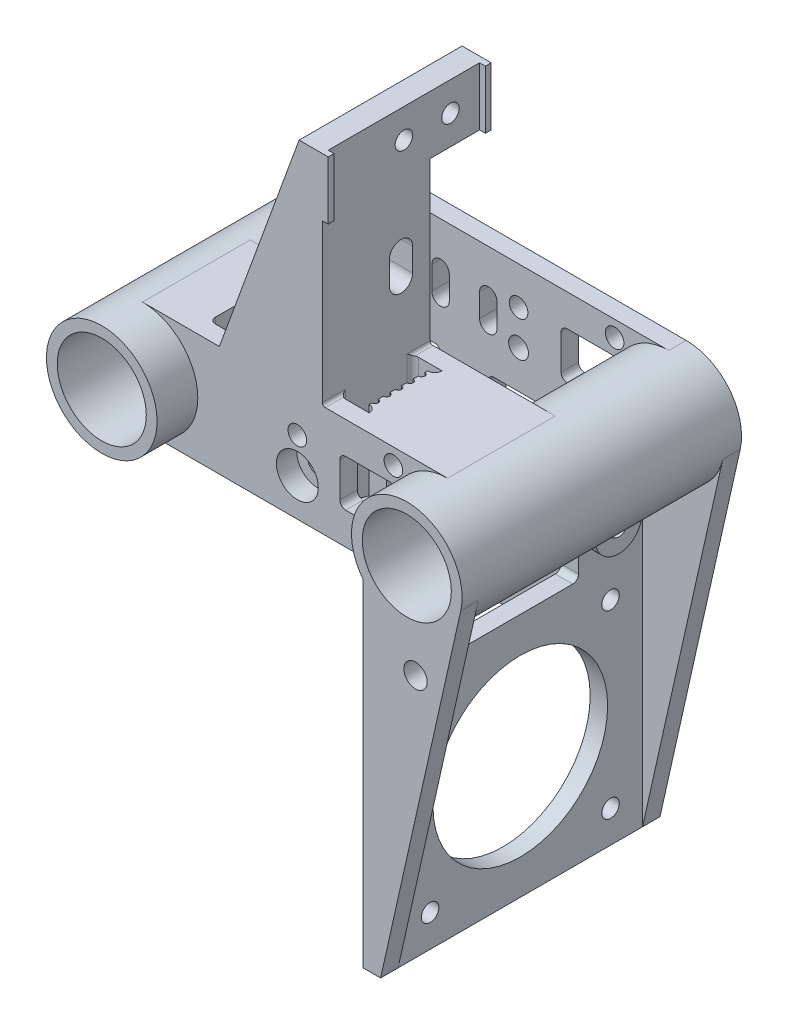
SolidWorks part; units mm, degrees
material "PET"
ref_plane "Front Plane" through (0, 0, 0) normal (0, 0, 1) x (1, 0, 0)
ref_plane "Top Plane" through (0, 0, 0) normal (0, 1, 0) x (1, 0, 0)
ref_plane "Right Plane" through (0, 0, 0) normal (1, 0, 0) x (0, 0, -1)
sketch "Sketch1" plane through (0, 0, 0) normal (0, 0, 1) x (1, 0, 0)
  circle A14 centre (0, 0) radius 7.65
  circle A15 centre (52.4, 0) radius 7.65
  circle A16 centre (0, 0) radius 9.5
  circle A17 centre (52.4, 0) radius 9.5
extrude "Boss-Extrude1" add sketch "Sketch1" along normal blind 48
sketch "Sketch29" plane through (0, 0, 0) normal (0, 0, -1) x (-1, 0, 0)
  line L5 (-42.3861, 4) -> (-34.9, 4)
  line L6 (-52.4, 9.5) -> (0, 9.5)
  line L7 (-33.9, 3) -> (-33.9, -3)
  line L9 (-34.9, -4) -> (-42.3861, -4)
  line L10 (-61.6706, -2.075) -> (-47.9, -63.6)
  line L12 (-47.9, -63.6) -> (-44.9, -63.6)
  line L13 (0.2114, -42.55) -> (9.2706, -2.075)
  line L21 (-44.9, -63.6) -> (-44.9, -42.55)
  line L24 (-44.9, -42.55) -> (0.2114, -42.55)
  line L25 (-7.5, -10.5) -> (-7.5, -24.5)
  line L26 (-12.2, -25.5) -> (-8.5, -25.5)
  line L27 (-13.2, -10.5) -> (-13.2, -24.5)
  line L28 (-12.2, -9.5) -> (-8.5, -9.5)
  line L30 (-11.7, 2) -> (-11.7, -2)
  line L32 (-14.7, 2) -> (-14.7, -2)
  line L35 (-21.4, -10.5) -> (-21.4, -24.5)
  line L36 (-19.9, 2) -> (-19.9, -2)
  line L37 (-22.9, 2) -> (-22.9, -2)
  line L38 (-44.9, -10.5) -> (-44.9, -24.5)
  line L39 (-43.9, -9.5) -> (-22.4, -9.5)
  line L40 (-43.9, -25.5) -> (-22.4, -25.5)
  arc A2 (-43.3861, 3) -> (-52.4, 9.5) centre (-52.4, 0) ccw
  arc A4 (-11.7, 2) -> (-14.7, 2) centre (-13.2, 2) ccw
  arc A6 (-42.3861, -4) -> (-43.3861, -3) centre (-42.3861, -3) cw
  arc A7 (-42.3861, 4) -> (-43.3861, 3) centre (-42.3861, 3) ccw
  arc A8 (-43.3861, -3) -> (-61.6706, -2.075) centre (-52.4, 0) cw
  arc A9 (-34.9, 4) -> (-33.9, 3) centre (-34.9, 3) cw
  arc A11 (-33.9, -3) -> (-34.9, -4) centre (-34.9, -3) cw
  arc A15 (9.2706, -2.075) -> (0, 9.5) centre (0, 0) cw
  arc A20 (-8.5, -9.5) -> (-7.5, -10.5) centre (-8.5, -10.5) cw
  arc A21 (-12.2, -9.5) -> (-13.2, -10.5) centre (-12.2, -10.5) ccw
  arc A22 (-13.2, -24.5) -> (-12.2, -25.5) centre (-12.2, -24.5) ccw
  arc A23 (-8.5, -25.5) -> (-7.5, -24.5) centre (-8.5, -24.5) ccw
  circle A24 centre (-10.3, -36.55) radius 1.5
  circle A25 centre (-24.3, -36.55) radius 1.5
  arc A27 (-14.7, -2) -> (-11.7, -2) centre (-13.2, -2) ccw
  arc A30 (-19.9, 2) -> (-22.9, 2) centre (-21.4, 2) ccw
  arc A31 (-22.9, -2) -> (-19.9, -2) centre (-21.4, -2) ccw
  arc A32 (-22.4, -9.5) -> (-21.4, -10.5) centre (-22.4, -10.5) cw
  arc A33 (-22.4, -25.5) -> (-21.4, -24.5) centre (-22.4, -24.5) ccw
  arc A34 (-43.9, -9.5) -> (-44.9, -10.5) centre (-43.9, -10.5) ccw
  arc A35 (-44.9, -24.5) -> (-43.9, -25.5) centre (-43.9, -24.5) ccw
  circle A36 centre (-43.0932, 6.75) radius 1.6
  circle A37 centre (-43.0932, -6.75) radius 1.6
  circle A38 centre (-26.5962, 3) radius 1.6
  circle A39 centre (-26.5962, -3) radius 1.7
extrude "Boss-Extrude18" add sketch "Sketch29" against normal blind 3
sketch "Sketch36" plane through (0, 0, 3) normal (0, 0, 1) x (1, 0, 0)
  line L0 (31.4, 9.5) -> (52.4, 9.5)
  line L1 (0, 9.5) -> (26.4, 9.5)
  line L2 (0, -9.5) -> (52.4, -9.5)
  line L3 (38.9, 3) -> (38.9, -3)
  line L4 (39.9, -4) -> (42.3861, -4)
  line L5 (39.9, 4) -> (42.3861, 4)
  line L6 (30.9, 10) -> (30.9, 37.05)
  line L7 (30.9, 37.05) -> (26.9, 37.05)
  line L8 (26.9, 37.05) -> (26.9, 10)
  arc A0 (0, 9.5) -> (0, -9.5) centre (0, 0) cw
  arc A1 (30.9, 10) -> (31.4, 9.5) centre (31.4, 10) ccw
  arc A2 (52.4, 9.5) -> (43.3861, 3) centre (52.4, 0) ccw
  arc A3 (26.9, 10) -> (26.4, 9.5) centre (26.4, 10) cw
  arc A4 (39.9, 4) -> (38.9, 3) centre (39.9, 3) ccw
  arc A7 (42.3861, 4) -> (43.3861, 3) centre (42.3861, 3) cw
  arc A8 (42.3861, -4) -> (43.3861, -3) centre (42.3861, -3) ccw
  arc A9 (38.9, -3) -> (39.9, -4) centre (39.9, -3) ccw
  arc A11 (43.3861, -3) -> (52.4, -9.5) centre (52.4, 0) ccw
  circle A13 centre (26.5962, -3) radius 1.7
  circle A14 centre (26.5962, 3) radius 1.6
  circle A15 centre (43.0932, -6.75) radius 1.6
  circle A16 centre (43.0932, 6.75) radius 1.6
  point P12 (30.9, 9.5)
extrude "Boss-Extrude26" add sketch "Sketch36" along normal blind 18.5 from offset 19.5
sketch "Sketch24" plane through (0, -9.5, 0) normal (0, -1, 0) x (1, 0, 0)
  line L14 (8.5, 37) -> (8.5, 26.5)
  line L15 (9.5, 25.5) -> (12.2, 25.5)
  line L27 (31.9, 38) -> (35.945, 38)
  line L28 (34.695, 33.195) -> (34.695, 32.305)
  line L29 (34.695, 31.195) -> (34.695, 30.305)
  line L30 (30.9, 26.5) -> (30.9, 37)
  line L31 (34.695, 28.305) -> (34.695, 29.195)
  line L32 (34.695, 34.305) -> (34.695, 35.195)
  line L33 (31.9, 25.5) -> (35.945, 25.5)
  line L34 (34.695, 36.75) -> (34.695, 36.305)
  line L35 (34.695, 27.195) -> (34.695, 26.75)
  line L36 (21.4, 37) -> (21.4, 35.4282)
  line L40 (9.5, 38) -> (20.4, 38)
  line L43 (12.2, 25.5) -> (14.6918, 25.5)
  arc A1 (8.5, 37) -> (9.5, 38) centre (9.5, 37) cw
  arc A3 (8.5, 26.5) -> (9.5, 25.5) centre (9.5, 26.5) ccw
  arc A15 (34.695, 36.305) -> (34.695, 35.195) centre (34.695, 35.75) cw
  arc A16 (34.695, 29.195) -> (34.695, 30.305) centre (34.695, 29.75) ccw
  arc A17 (34.695, 31.195) -> (34.695, 32.305) centre (34.695, 31.75) ccw
  arc A18 (34.695, 33.195) -> (34.695, 34.305) centre (34.695, 33.75) ccw
  arc A19 (34.695, 27.195) -> (34.695, 28.305) centre (34.695, 27.75) ccw
  arc A20 (30.9, 26.5) -> (31.9, 25.5) centre (31.9, 26.5) ccw
  arc A21 (30.9, 37) -> (31.9, 38) centre (31.9, 37) cw
  arc A22 (35.945, 38) -> (34.695, 36.75) centre (34.695, 38) cw
  arc A23 (34.695, 26.75) -> (35.945, 25.5) centre (34.695, 25.5) cw
  arc A30 (21.4, 37) -> (20.4, 38) centre (20.4, 37) ccw
  arc A31 (21.4, 35.4282) -> (20.5429, 34.4385) centre (20.4, 35.4282) cw
  arc A32 (20.5429, 34.4385) -> (15.6501, 26.7857) centre (21.4, 28.5) ccw
  arc A33 (14.6918, 25.5) -> (15.6501, 26.7857) centre (14.6918, 26.5) ccw
extrude "Cut-Extrude15" cut sketch "Sketch24" against normal up to surface (46.55 mm away) up to face at (28.9, 37.05, 31.75)
sketch "Sketch14" plane through (0, -9.5, 0) normal (0, -1, 0) x (1, 0, 0)
  circle A0 centre (21.4, 28.5) radius 4.125
extrude "Boss-Extrude27" add sketch "Sketch14" along normal blind 4
sketch "Sketch37" plane through (13.2, 0, 0) normal (-1, 0, 0) x (0, 0, 1)
  line L0 (3, -25.5) -> (3, -10)
  line L3 (22.5, 9.5) -> (3, -10)
  line L4 (22.5, 9.5) -> (22.5, -9.5)
  line L7 (3, -25.5) -> (20.0185, -8.4815)
  arc A1 (22.5, -9.5) -> (20.0185, -8.4815) centre (21.0502, -9.5) ccw
extrude "Boss-Extrude28" add sketch "Sketch37" against normal up to surface (8.2 mm away) up to face at (21.4, -17.5, 1.5)
sketch "Sketch34" plane through (0, 9.5, 0) normal (0, 1, 0) x (1, 0, 0)
  circle A2 centre (21.4, -28.5) radius 4.175
extrude "Cut-Extrude17" cut sketch "Sketch34" against normal blind 4.5
sketch "Sketch38" plane through (0, 5, 0) normal (0, 1, 0) x (1, 0, 0)
  circle A1 centre (21.4, -28.5) radius 2.15
extrude "Cut-Extrude18" cut sketch "Sketch38" against normal up to surface (18.5 mm away) up to face at (21.4, -13.5, 24.375)
sketch "Sketch7" plane through (0, 0, 48) normal (0, 0, 1) x (1, 0, 0)
  line L8 (61.6706, -2.075) -> (47.9, -63.6)
  line L10 (44.9, -5.831) -> (44.9, -63.6)
  line L11 (47.9, -63.6) -> (44.9, -63.6)
  circle A2 centre (53.9, -15.6) radius 2
  arc A8 (61.6706, -2.075) -> (44.9, -5.831) centre (52.4, 0) cw
extrude "Boss-Extrude30" add sketch "Sketch7" against normal blind 3
sketch "Sketch39" plane through (0, 0, 3) normal (0, 0, 1) x (1, 0, 0)
  line L0 (44.9, -63.6) -> (44.9, -21.5)
  line L2 (47.9, -21.5) -> (47.9, -63.6)
  line L3 (47.9, -63.6) -> (44.9, -63.6)
  line L5 (47.9, -21.5) -> (44.9, -21.5)
extrude "Boss-Extrude31" add sketch "Sketch39" along normal up to surface (42 mm away) up to face at (51.9, -15.6, 45)
sketch "Sketch61" plane through (0, 0, 3) normal (0, 0, 1) x (1, 0, 0)
  line L0 (52.4, -9.5) -> (47.9, -9.5)
  line L1 (44.9, -5.831) -> (44.9, -21.5)
  line L2 (44.9, -21.5) -> (47.9, -21.5)
  line L3 (47.9, -21.5) -> (47.9, -9.5)
  arc A0 (44.9, -5.831) -> (52.4, -9.5) centre (52.4, 0) ccw
extrude "Boss-Extrude39" add sketch "Sketch61" along normal blind 11
sketch "Sketch40" plane through (0, 0, 45) normal (0, 0, -1) x (-1, 0, 0)
  line L12 (-51.45, -12) -> (-50.5, -12)
  line L13 (-51.45, -12) -> (-51.45, -19)
  line L14 (-51.45, -19) -> (-50.5, -19)
  line L15 (-50.5, -12) -> (-50.5, -19)
  line L16 (-49.4, -12) -> (-47.9, -12)
  line L17 (-49.4, -12) -> (-49.4, -19)
  line L18 (-49.4, -19) -> (-47.9, -19)
  line L19 (-47.9, -12) -> (-47.9, -19)
extrude "Boss-Extrude32" add sketch "Sketch40" along normal blind 0.3
sketch "Sketch47" plane through (47.9, 0, 0) normal (1, 0, 0) x (0, 0, -1)
  circle A0 centre (-8.5, -15.55) radius 1.5
  circle A1 centre (-8.5, -15.55) radius 4
extrude "Boss-Extrude40" add sketch "Sketch47" along normal blind 1.4
sketch "Sketch20" plane through (47.9, 0, 0) normal (1, 0, 0) x (0, 0, -1)
  circle A0 centre (-8.5, -58.1) radius 1.5
  circle A1 centre (-39.5, -58.1) radius 1.5
  circle A2 centre (-8.5, -27.1) radius 1.5
  circle A3 centre (-24, -42.6) radius 15
  circle A5 centre (-8.5, -15.55) radius 1.5
extrude "Cut-Extrude19" cut sketch "Sketch20" against normal up to surface (3 mm away) up to face at (44.9, -24.9017, 16.1429)
sketch "Sketch43" plane through (0, 0, 41) normal (0, 0, 1) x (1, 0, 0)
  circle A1 centre (26.5962, -3) radius 3.6
extrude "Cut-Extrude22" cut sketch "Sketch43" against normal blind 3.5
sketch "Sketch45" plane through (0, 0, 41) normal (0, 0, 1) x (1, 0, 0)
  line L0 (33.9, 3) -> (33.9, -3)
  line L1 (34.9, 4) -> (42.3861, 4)
  line L2 (34.9, -4) -> (42.3861, -4)
  arc A0 (42.3861, 4) -> (43.3861, 3) centre (42.3861, 3) cw
  arc A1 (43.3861, 3) -> (42.3861, 4) centre (42.3861, 3) ccw construction
  arc A2 (42.3861, -4) -> (43.3861, -3) centre (42.3861, -3) ccw
  arc A3 (61.6706, -2.075) -> (44.9, -5.831) centre (52.4, 0) ccw construction
  arc A4 (33.9, -3) -> (34.9, -4) centre (34.9, -3) ccw
  arc A6 (33.9, 3) -> (34.9, 4) centre (34.9, 3) cw
  arc A8 (43.3861, -3) -> (43.3861, 3) centre (52.4, 0) cw
sketch "Sketch48" plane through (44.9, 0, 0) normal (-1, 0, 0) x (0, 0, 1)
  line L7 (11.7332, -15.55) -> (10.1166, -12.75)
  line L8 (10.1166, -12.75) -> (6.8834, -12.75)
  line L9 (6.8834, -12.75) -> (5.2668, -15.55)
  line L10 (5.2668, -15.55) -> (6.8834, -18.35)
  line L11 (6.8834, -18.35) -> (10.1166, -18.35)
  line L12 (10.1166, -18.35) -> (11.7332, -15.55)
  circle A0 centre (8.5, -15.55) radius 2.8 construction
extrude "Cut-Extrude24" cut sketch "Sketch48" against normal blind 2
extrude "Cut-Extrude25" cut sketch "Sketch45" against normal up to surface (3 mm away) up to face at (33.9225, 0, 38)
sketch "Sketch51" plane through (0, 37.05, 0) normal (0, 1, 0) x (1, 0, 0)
  line L1 (26.9, -41) -> (30.9, -41)
  line L2 (26.9, -41) -> (26.9, -13)
  line L3 (26.9, -13) -> (30.9, -13)
  line L4 (30.9, -41) -> (30.9, -13)
extrude "Boss-Extrude35" add sketch "Sketch51" along normal blind 10
sketch "Sketch52" plane through (30.9, 0, 0) normal (1, 0, 0) x (0, 0, -1)
  line L8 (-13, 47.05) -> (-13, 37.05) construction
  line L9 (-41, 47.05) -> (-40, 47.05)
  line L10 (-41, 47.05) -> (-41, 37.05)
  line L11 (-41, 37.05) -> (-40, 37.05)
  line L12 (-40, 47.05) -> (-40, 37.05)
  line L13 (-14, 47.05) -> (-13, 47.05)
  line L14 (-14, 47.05) -> (-14, 37.05)
  line L15 (-14, 37.05) -> (-13, 37.05)
  line L16 (-13, 47.05) -> (-13, 37.05)
sketch "Sketch53" plane through (30.9, 0, 0) normal (1, 0, 0) x (0, 0, -1)
  line L3 (-29.5, 25.525) -> (-29.5, 21.525)
  line L5 (-25.5, 25.525) -> (-25.5, 21.525)
  circle A0 centre (-19, 42.05) radius 1.5
  circle A1 centre (-27, 42.05) radius 1.5
  arc A22 (-25.5, 25.525) -> (-29.5, 25.525) centre (-27.5, 25.525) ccw
  arc A23 (-29.5, 21.525) -> (-25.5, 21.525) centre (-27.5, 21.525) ccw
extrude "Cut-Extrude29" cut sketch "Sketch53" against normal up to vertex (4.5 mm away) from vertex up to point (26.4, 9.5, 41) starting at point (31.4, 9.5, 37.866)
sketch "Sketch54" plane through (26.9, 0, 0) normal (-1, 0, 0) x (0, 0, 1)
  line L0 (19, 45.2832) -> (16.2, 43.6666)
  line L13 (16.2, 43.6666) -> (16.2, 40.4334)
  line L14 (16.2, 40.4334) -> (19, 38.8168)
  line L15 (19, 38.8168) -> (21.8, 40.4334)
  line L16 (21.8, 40.4334) -> (21.8, 43.6666)
  line L17 (21.8, 43.6666) -> (19, 45.2832)
  line L18 (27, 45.2832) -> (24.2, 43.6666)
  line L19 (24.2, 43.6666) -> (24.2, 40.4334)
  line L20 (24.2, 40.4334) -> (27, 38.8168)
  line L21 (27, 38.8168) -> (29.8, 40.4334)
  line L22 (29.8, 40.4334) -> (29.8, 43.6666)
  line L23 (29.8, 43.6666) -> (27, 45.2832)
  circle A0 centre (19, 42.05) radius 2.8 construction
  circle A1 centre (27, 42.05) radius 2.8 construction
extrude "Cut-Extrude28" cut sketch "Sketch54" against normal blind 1.5
extrude "Boss-Extrude36" add sketch "Sketch52" along normal blind 1
sketch "Sketch56" plane through (0, -9.5, 0) normal (0, -1, 0) x (1, 0, 0)
  line L2 (34.695, 37) -> (34.695, 26.5)
  line L4 (33.695, 25.5) -> (35.945, 25.5)
  line L5 (35.945, 25.5) -> (35.945, 38)
  line L6 (35.945, 38) -> (33.695, 38)
  arc A0 (33.695, 25.5) -> (34.695, 26.5) centre (33.695, 26.5) ccw
  arc A1 (34.695, 37) -> (33.695, 38) centre (33.695, 37) ccw
extrude "Boss-Extrude37" add sketch "Sketch56" against normal up to surface (5.5 mm away) up to face at (38.6167, -4, 34.4286)
sketch "Sketch59" plane through (0, 0, 41) normal (0, 0, 1) x (1, 0, 0)
  line L1 (26.9, 47.05) -> (13.2, 9.5)
  line L7 (13.2, 9.5) -> (26.9, 9.5)
  line L8 (26.9, 9.5) -> (26.9, 47.05)
extrude "Boss-Extrude38" add sketch "Sketch59" against normal blind 3
fillet "Fillet1" radius 1 2 edges at (46.4, -21.5, 14) (46.4, -21.5, 45)
